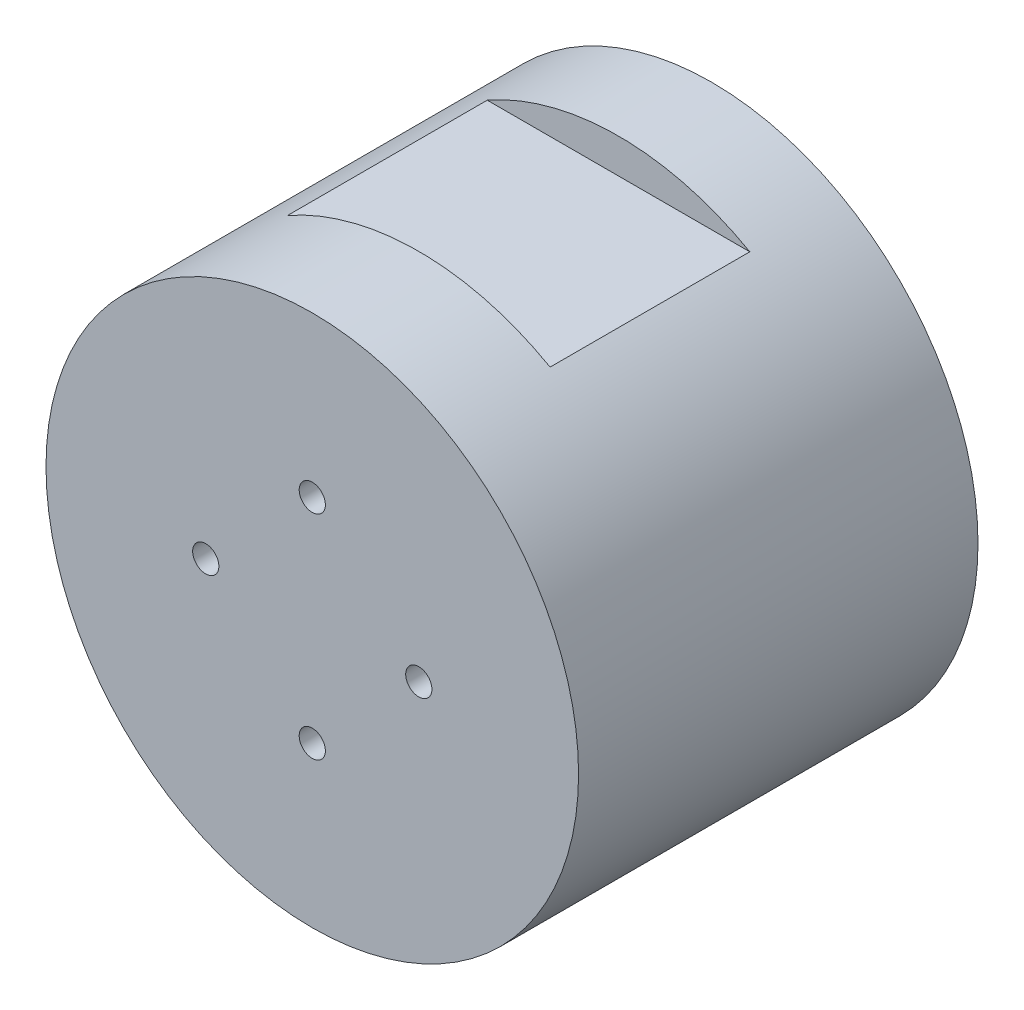
SolidWorks part; units mm, degrees
ref_plane "Front Plane" through (0, 0, 0) normal (0, 0, 1) x (1, 0, 0)
ref_plane "Top Plane" through (0, 0, 0) normal (0, 1, 0) x (1, 0, 0)
ref_plane "Right Plane" through (0, 0, 0) normal (1, 0, 0) x (0, 0, -1)
sketch "Sketch1" plane through (0, 0, 0) normal (0, 0, 1) x (1, 0, 0)
  circle A0 centre (0, 0) radius 25.4
  dimension "D1" = 50.8
extrude "Boss-Extrude1" add sketch "Sketch1" along normal blind 38.1
sketch "Sketch2" plane through (0, 0, 0) normal (0, 0, -1) x (-1, 0, 0)
  circle A0 centre (0, 0) radius 17.6759
  dimension "D1" = 35.3517
extrude "Cut-Extrude1" cut sketch "Sketch2" against normal blind 31.75
thread "Thread1" pitch 2.1167 method cut profile "Thread Profile1" start angle 0, offset 2.54, length 30.48, pitch 2.1167, diameter 35.3517
ref_plane "Plane1" through (17.6759, 0, -2.54) normal (0, -1, 0) x (1, 0, 0)
sketch "Thread Profile1" plane through (17.6759, 0, -2.54) normal (0, -1, 0) x (1, 0, 0)
  line L0 (0, 0) -> (0, 2.1167) construction
  line L1 (0, 0) -> (1.1457, 0.6615)
  line L2 (1.1457, 0.6615) -> (1.1457, 0.926)
  line L3 (1.1457, 0.926) -> (0, 1.5875)
  line L4 (1.1457, 0.7937) -> (0, 0.7937) construction
  line L11 (0, 0) -> (0, 1.5875)
  point P2 (0, 0)
  dimension "Pitch" = 2.1167
  dimension "Profile_Angle" = 60
  dimension "Profile_Land" = 0.2646
  dimension "Profile_Height" = 1.1457
sketch "Sketch6" plane through (0, 0, 0) normal (1, 0, 0) x (0, 0, -1)
  line L0 (0, 25.4) -> (-38.1, 25.4) construction
  line L1 (-8.89, 25.4) -> (-27.94, 25.4)
  line L2 (-8.89, 25.4) -> (-8.89, 22.098)
  line L3 (-8.89, 22.098) -> (-27.94, 22.098)
  line L4 (-27.94, 25.4) -> (-27.94, 22.098)
  line L5 (-8.89, 25.4) -> (-27.94, 22.098) construction
  line L6 (-8.89, 22.098) -> (-27.94, 25.4) construction
  line L7 (-38.1, -25.4) -> (0, -25.4) construction
  line L8 (-8.89, -25.4) -> (-27.94, -25.4)
  line L9 (-8.89, -25.4) -> (-8.89, -22.098)
  line L10 (-8.89, -22.098) -> (-27.94, -22.098)
  line L11 (-27.94, -25.4) -> (-27.94, -22.098)
  line L12 (-8.89, -25.4) -> (-27.94, -22.098) construction
  line L13 (-8.89, -22.098) -> (-27.94, -25.4) construction
  line L14 (0, -25.4) -> (0, 25.4) construction
  point P4 (-18.415, 23.749)
  point P11 (-18.415, -23.749)
  dimension "D1" = 44.196
  dimension "D2" = 8.89
  dimension "D3" = 19.05
extrude "Cut-Extrude3" cut sketch "Sketch6" against normal up to next and the other way up to next
sketch "Sketch7" plane through (0, 0, 31.75) normal (0, 0, -1) x (-1, 0, 0)
  circle A0 centre (0, 0) radius 12.7 construction
  circle A1 centre (0, 0) radius 10.16 construction
  circle A2 centre (0, 10.16) radius 1.25
  circle A3 centre (10.16, 0) radius 1.25
  circle A4 centre (0, -10.16) radius 1.25
  circle A5 centre (-10.16, 0) radius 1.25
  point P12 (0, 0)
  dimension "D1" = 25.4
  dimension "D2" = 20.32
  dimension "D3" = 2.5
  dimension "D4" = 4
extrude "Cut-Extrude4" cut sketch "Sketch7" against normal up to next
